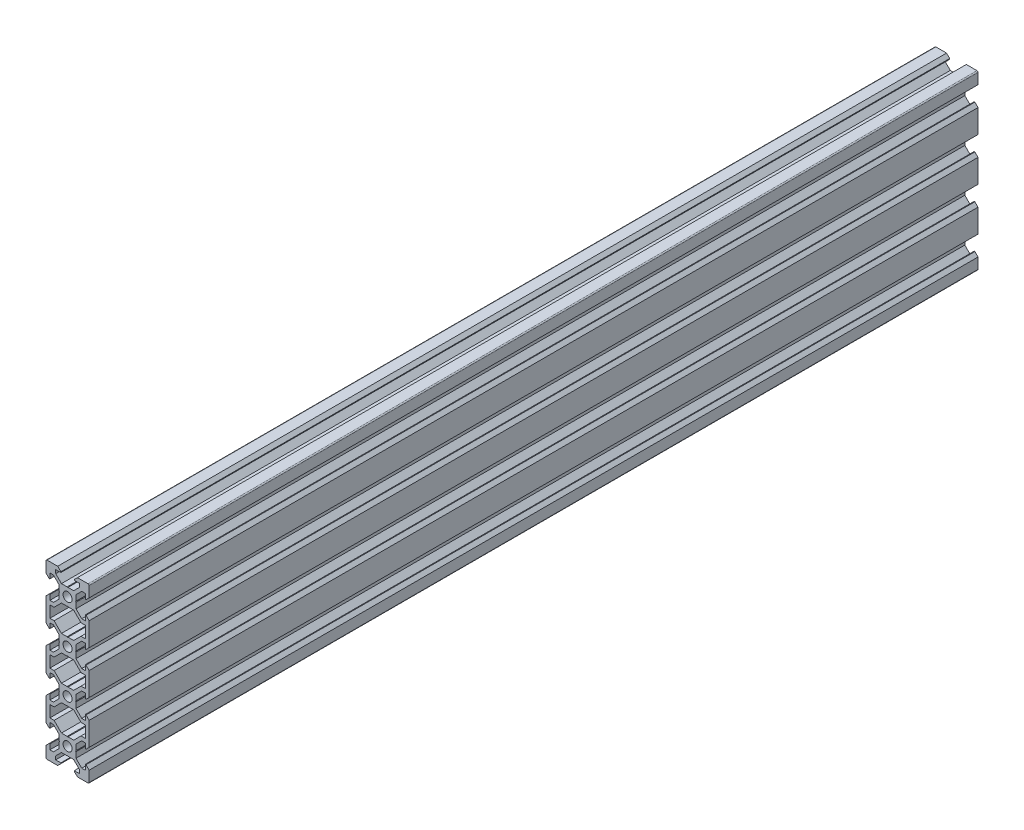
SolidWorks part; units mm, degrees
ref_plane "Plan de face" through (0, 0, 0) normal (0, 0, 1) x (1, 0, 0)
ref_plane "Plan de dessus" through (0, 0, 0) normal (0, 1, 0) x (1, 0, 0)
ref_plane "Plan de droite" through (0, 0, 0) normal (1, 0, 0) x (0, 0, -1)
ref_axis "Axe" through (0, 0, -13.782) along (0, 0, 1)
sketch "Esquisse1" plane through (0, 0, 0) normal (0, 0, 1) x (1, 0, 0)
  line L0 (0, 27.6392) -> (0, -27.6392) construction
  line L1 (-33.6074, 0) -> (33.6074, 0) construction
  line L2 (0, 0) -> (-22.2114, 22.2114) construction
  line L3 (-9.5, 10) -> (-4.58, 10)
  line L4 (-4.58, 10) -> (-3.125, 8.545)
  line L5 (-3.125, 8.545) -> (-3.125, 8.2)
  line L6 (-3.125, 8.2) -> (-5.5, 8.2)
  line L7 (-2.8393, 3.9) -> (-5.5, 6.5607)
  line L8 (-2.8393, 3.9) -> (-0.21, 3.9)
  line L9 (-5.5, 6.5607) -> (-5.5, 8.2)
  line L10 (0, 3.69) -> (0, 2.1)
  line L11 (-3.9, 2.8393) -> (-6.5607, 5.5)
  line L12 (-8.545, 3.125) -> (-8.2, 3.125)
  line L13 (-8.2, 3.125) -> (-8.2, 5.5)
  line L14 (-6.5607, 5.5) -> (-8.2, 5.5)
  line L15 (-10, 4.58) -> (-8.545, 3.125)
  line L16 (-10, 9.5) -> (-10, 4.58)
  line L17 (-0.21, 3.9) -> (0, 3.69)
  line L18 (-3.9, 2.8393) -> (-3.9, 0.21)
  line L19 (-6.2393, -12.7) -> (-8.2, -12.7)
  line L20 (-3.9, 0.21) -> (-3.69, 0)
  line L21 (-0.21, -3.9) -> (0, -3.69)
  line L22 (0, -3.69) -> (0, -2.1)
  line L23 (-6.5607, -5.5) -> (-8.2, -5.5)
  line L24 (-2.8393, -3.9) -> (-0.21, -3.9)
  line L25 (-8.545, -3.125) -> (-8.2, -3.125)
  line L26 (-10, -4.58) -> (-8.545, -3.125)
  line L27 (-8.2, -3.125) -> (-8.2, -5.5)
  line L28 (-2.8393, -3.9) -> (-6.2393, -7.3)
  line L29 (-3.9, -2.8393) -> (-6.5607, -5.5)
  line L30 (-3.9, -2.8393) -> (-3.9, -0.21)
  line L31 (-3.9, -0.21) -> (-3.69, 0)
  line L32 (-6.2393, -7.3) -> (-8.2, -7.3)
  line L33 (-8.2, -7.3) -> (-8.2, -12.7)
  line L34 (-8.2, -10) -> (-10, -10) construction
  line L35 (-10, -15.42) -> (-10, -4.58)
  line L36 (-3.9, -19.79) -> (-3.69, -20)
  line L37 (-3.9, -17.1607) -> (-3.9, -19.79)
  line L38 (-3.9, -17.1607) -> (-6.5607, -14.5)
  line L39 (-2.8393, -16.1) -> (-6.2393, -12.7)
  line L40 (-8.2, -16.875) -> (-8.2, -14.5)
  line L41 (-10, -15.42) -> (-8.545, -16.875)
  line L42 (-8.545, -16.875) -> (-8.2, -16.875)
  line L43 (-2.8393, -16.1) -> (-0.21, -16.1)
  line L44 (-6.5607, -14.5) -> (-8.2, -14.5)
  line L45 (0, -16.31) -> (0, -17.9)
  line L46 (-0.21, -16.1) -> (0, -16.31)
  line L47 (-8.2, -30) -> (-10, -30) construction
  line L48 (-3.69, -20) -> (0, -20) construction
  line L49 (-0.21, -23.9) -> (0, -23.69)
  line L50 (0, -23.69) -> (0, -22.1)
  line L51 (-6.5607, -25.5) -> (-8.2, -25.5)
  line L52 (-2.8393, -23.9) -> (-0.21, -23.9)
  line L53 (-8.545, -23.125) -> (-8.2, -23.125)
  line L54 (-10, -24.58) -> (-8.545, -23.125)
  line L55 (-8.2, -23.125) -> (-8.2, -25.5)
  line L56 (-2.8393, -23.9) -> (-6.2393, -27.3)
  line L57 (-3.9, -22.8393) -> (-6.5607, -25.5)
  line L58 (-3.9, -22.8393) -> (-3.9, -20.21)
  line L59 (-3.9, -20.21) -> (-3.69, -20)
  line L60 (-10, -24.58) -> (-10, -35.42)
  line L61 (-8.2, -32.7) -> (-8.2, -27.3)
  line L62 (-3.69, -40) -> (0, -40) construction
  line L63 (-8.2, -50) -> (-10, -50) construction
  line L64 (0, -60) -> (-22.2114, -82.2114) construction
  line L65 (-33.6074, -60) -> (33.6074, -60) construction
  line L66 (0, -87.6392) -> (0, -32.3608) construction
  line L67 (-6.2393, -32.7) -> (-8.2, -32.7)
  line L68 (-3.9, -39.79) -> (-3.69, -40)
  line L69 (-3.9, -37.1607) -> (-3.9, -39.79)
  line L70 (-3.9, -37.1607) -> (-6.5607, -34.5)
  line L71 (-2.8393, -36.1) -> (-6.2393, -32.7)
  line L72 (-8.2, -36.875) -> (-8.2, -34.5)
  line L73 (-10, -35.42) -> (-8.545, -36.875)
  line L74 (-8.545, -36.875) -> (-8.2, -36.875)
  line L75 (-6.2393, -27.3) -> (-8.2, -27.3)
  line L76 (-2.8393, -36.1) -> (-0.21, -36.1)
  line L77 (-6.5607, -34.5) -> (-8.2, -34.5)
  line L78 (0, -36.31) -> (0, -37.9)
  line L79 (-0.21, -36.1) -> (0, -36.31)
  line L80 (-0.21, -43.9) -> (0, -43.69)
  line L81 (0, -43.69) -> (0, -42.1)
  line L82 (-6.5607, -45.5) -> (-8.2, -45.5)
  line L83 (-2.8393, -43.9) -> (-0.21, -43.9)
  line L84 (-8.545, -43.125) -> (-8.2, -43.125)
  line L85 (-10, -44.58) -> (-8.545, -43.125)
  line L86 (-8.2, -43.125) -> (-8.2, -45.5)
  line L87 (-2.8393, -43.9) -> (-6.2393, -47.3)
  line L88 (-3.9, -42.8393) -> (-6.5607, -45.5)
  line L89 (-3.9, -42.8393) -> (-3.9, -40.21)
  line L90 (-3.9, -40.21) -> (-3.69, -40)
  line L91 (-10, -44.58) -> (-10, -55.42)
  line L92 (-8.2, -52.7) -> (-8.2, -47.3)
  line L93 (-6.2393, -52.7) -> (-8.2, -52.7)
  line L94 (-3.9, -59.79) -> (-3.69, -60)
  line L95 (-3.9, -57.1607) -> (-3.9, -59.79)
  line L96 (-3.9, -57.1607) -> (-6.5607, -54.5)
  line L97 (-2.8393, -56.1) -> (-6.2393, -52.7)
  line L98 (-8.2, -56.875) -> (-8.2, -54.5)
  line L99 (-10, -55.42) -> (-8.545, -56.875)
  line L100 (-8.545, -56.875) -> (-8.2, -56.875)
  line L101 (-2.8393, -56.1) -> (-0.21, -56.1)
  line L102 (-6.5607, -54.5) -> (-8.2, -54.5)
  line L103 (0, -56.31) -> (0, -57.9)
  line L104 (-0.21, -56.1) -> (0, -56.31)
  line L105 (-3.9, -60.21) -> (-3.69, -60)
  line L106 (-6.2393, -47.3) -> (-8.2, -47.3)
  line L107 (-3.9, -62.8393) -> (-3.9, -60.21)
  line L108 (-0.21, -63.9) -> (0, -63.69)
  line L109 (-10, -69.5) -> (-10, -64.58)
  line L110 (-10, -64.58) -> (-8.545, -63.125)
  line L111 (-6.5607, -65.5) -> (-8.2, -65.5)
  line L112 (-8.2, -63.125) -> (-8.2, -65.5)
  line L113 (-8.545, -63.125) -> (-8.2, -63.125)
  line L114 (-3.9, -62.8393) -> (-6.5607, -65.5)
  line L115 (0, -63.69) -> (0, -62.1)
  line L116 (-5.5, -66.5607) -> (-5.5, -68.2)
  line L117 (-2.8393, -63.9) -> (-0.21, -63.9)
  line L118 (-2.8393, -63.9) -> (-5.5, -66.5607)
  line L119 (-3.125, -68.2) -> (-5.5, -68.2)
  line L120 (-3.125, -68.545) -> (-3.125, -68.2)
  line L121 (-4.58, -70) -> (-3.125, -68.545)
  line L122 (-9.5, -70) -> (-4.58, -70)
  arc A0 (0, -2.1) -> (0, 2.1) centre (0, 0) cw
  arc A1 (-9.5, 10) -> (-10, 9.5) centre (-9.5, 9.5) ccw
  arc A2 (0, -42.1) -> (0, -37.9) centre (0, -40) cw
  arc A3 (-9.5, -70) -> (-10, -69.5) centre (-9.5, -69.5) cw
  arc A4 (0, -17.9) -> (0, -22.1) centre (0, -20) ccw
  arc A5 (0, -57.9) -> (0, -62.1) centre (0, -60) ccw
  point P4 (0, 0)
  point P7 (0, 0)
  point P30 (-10, 10)
  point P60 (0, -20)
  point P146 (-10, -70)
  dimension "D5" = 11
  dimension "D2" = 2.1
  dimension "D3" = 6.25
  dimension "D10" = 0.5
  dimension "D4" = 9.16
  dimension "D6" = 1.5
  dimension "D7" = 1.8
  dimension "D8" = 4.3
  dimension "D9" = 20
  dimension "D11" = 0.42
  dimension "D12" = 10
  dimension "D13" = 1.8
extrude "Boss.-Extru.1" add sketch "Esquisse1" along normal blind 412
sketch "Esquisse3" plane through (0, 0, 412) normal (0, 0, 1) x (1, 0, 0)
  line L0 (0, 0) -> (-9.8536, 9.8536) construction
  line L1 (-8.2, 8.2) -> (-8.2, 6.57)
  line L2 (-8.2, 6.57) -> (-7.54, 6.57)
  line L3 (-7.54, 6.57) -> (-6.57, 7.54)
  line L4 (-8.2, 3.125) -> (-8.2, 5.5) construction
  line L5 (-6.57, 8.2) -> (-6.57, 7.54)
  line L6 (-8.2, 8.2) -> (-6.57, 8.2)
  line L7 (-5.5, 6.5607) -> (-5.5, 8.2) construction
  line L8 (-10, -30) -> (6.918, -30) construction
  line L9 (-10, -24.58) -> (-10, -35.42) construction
  line L10 (-8.2, -68.2) -> (-6.57, -68.2)
  line L11 (-6.57, -68.2) -> (-6.57, -67.54)
  line L12 (-7.54, -66.57) -> (-6.57, -67.54)
  line L13 (-8.2, -66.57) -> (-7.54, -66.57)
  line L14 (-8.2, -68.2) -> (-8.2, -66.57)
  arc A0 (-9.5, 10) -> (-10, 9.5) centre (-9.5, 9.5) ccw construction
  point P13 (-7.055, 7.055)
  point P14 (-6.57, 7.87)
  point P26 (-7.055, -67.055)
  dimension "D1" = 1.07
extrude "Enlèv. mat.-Extru.1" [suppressed] cut sketch "Esquisse3" against normal through all
mirror "Symétrie1" about plane through (0, 3.69, 412) normal (-1, 0, 0) of "Enlèv. mat.-Extru.1", "Boss.-Extru.1"
